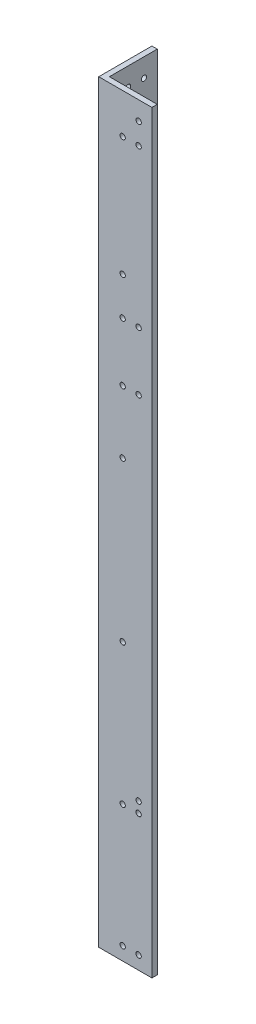
SolidWorks part; units mm, degrees
ref_plane "Front Plane" through (0, 0, 0) normal (0, 0, 1) x (1, 0, 0)
ref_plane "Top Plane" through (0, 0, 0) normal (0, 1, 0) x (1, 0, 0)
ref_plane "Right Plane" through (0, 0, 0) normal (1, 0, 0) x (0, 0, -1)
sketch "Sketch2" plane through (0, 0, 0) normal (0, 1, 0) x (1, 0, 0)
  line L0 (0, 31.75) -> (3.175, 31.75)
  line L1 (3.175, 31.75) -> (3.175, 3.175)
  line L2 (3.175, 3.175) -> (31.75, 3.175)
  line L3 (31.75, 3.175) -> (31.75, 0)
  line L4 (31.75, 0) -> (0, 0)
  line L5 (0, 0) -> (0, 31.75)
  point P9 (1.5875, 31.75)
  point P10 (31.75, 1.5875)
  dimension "D4" = 3.175
  dimension "D1" = 31.75
  dimension "D2" = 31.75
  dimension "D3" = 3.175
extrude "Boss-Extrude1" add sketch "Sketch2" along normal blind 450
sketch "RightSideHoles-Sketch3" plane through (0, 0, 0) normal (0, 0, 1) x (1, 0, 0)
  line L0 (0, 0) -> (31.75, 0) construction
  line L1 (0, 450) -> (31.75, 450) construction
  line L3 (0, 450) -> (0, 0) construction
  circle A0 centre (14.2875, 81.1125) radius 1.5875
  circle A1 centre (23.8125, 81.1125) radius 1.5875
  circle A3 centre (23.8125, 87.4625) radius 1.5875
  circle A5 centre (14.2875, 426.1875) radius 1.5875
  circle A6 centre (23.8125, 438.8875) radius 1.5875
  circle A7 centre (23.8125, 426.1875) radius 1.5875
  circle A8 centre (14.2875, 332.3776) radius 1.5875
  circle A9 centre (23.8125, 332.3776) radius 1.5875
  circle A10 centre (14.2875, 297.4526) radius 1.5875
  circle A11 centre (23.8125, 297.4526) radius 1.5875
  circle A12 centre (14.2875, 7.9375) radius 1.5875
  circle A13 centre (23.8125, 7.9375) radius 1.5875
  circle A14 centre (14.2875, 165) radius 1.5875
  circle A15 centre (14.2875, 260) radius 1.5875
  circle A16 centre (14.2875, 355) radius 1.5875
  dimension "D4" = 3.175
  dimension "D1" = 81.1125
  dimension "D2" = 14.2875
  dimension "D12" = 7.9375
  dimension "D7" = 34.925
  dimension "D3" = 9.525
  dimension "D10" = 332.3776
  dimension "D11" = 165
  dimension "D13" = 95
  dimension "D5" = 6.35
  dimension "D6" = 12.7
  dimension "D8" = 11.1125
  dimension "D9" = 95
sketch "FrontSideHoles-Sketch4" plane through (0, 0, 0) normal (-1, 0, 0) x (0, 0, 1)
  line L0 (-31.75, 450) -> (0, 450) construction
  line L1 (0, 450) -> (0, 0) construction
  line L3 (-31.75, 0) -> (0, 0) construction
  circle A0 centre (-23.8125, 81.1125) radius 1.5875
  circle A2 centre (-23.8125, 87.4625) radius 1.5875
  circle A3 centre (-14.2875, 87.4625) radius 1.5875
  circle A4 centre (-23.8125, 438.8875) radius 1.5875
  circle A5 centre (-14.2875, 438.8875) radius 1.5875
  circle A6 centre (-23.8125, 426.1875) radius 1.5875
  circle A8 centre (-14.2875, 350.0151) radius 2
  circle A9 centre (-14.2875, 309.8151) radius 2
  circle A10 centre (-14.2875, 165) radius 1.5875
  circle A11 centre (-14.2875, 260) radius 1.5875
  circle A13 centre (-23.8125, 7.9375) radius 1.5875
  circle A14 centre (-14.2875, 7.9375) radius 1.5875
  dimension "D4" = 3.175
  dimension "D13" = 95
  dimension "D5" = 6.35
  dimension "D16" = 4
  dimension "D6" = 11.1125
  dimension "D9" = 40.2
  dimension "D10" = 14.2875
  dimension "D7" = 12.7
  dimension "D8" = 309.8151
  dimension "D12" = 165
  dimension "D15" = 7.9375
  dimension "D2" = 14.2875
  dimension "D11" = 9.525
  dimension "D3" = 81.1125
extrude "RightSideHoles-Cut-Extrude1" cut sketch "RightSideHoles-Sketch3" against normal blind 3.175
extrude "FrontSideHoles-Cut-Extrude2" cut sketch "FrontSideHoles-Sketch4" against normal blind 3.175
equation "\"RailThickness\"= .125in'Spec"
equation "\"VSWidth\"= 1.25in'Spec"
equation "\"VSHeight\"= 1.25in'Spec"
equation "\"VSLength\"= 450mm"
equation "\"HoleOffsetFromEdge\"= \"RailThickness\" * 2.5"
equation "\"HoleOffsetFromSide\"= \"RailThickness\" * 3.5"
equation "\"LegHeight\"= 70mm'Space needed for PSU/Stepper/Electronics"
equation "\"VSBottomSideRailHoleY1FromBottomOfLowerRail\"= \"V1 BottomOfLowerRail\" + \"HoleOffsetFromSide\"'Equals 81.1125"
equation "\"VSSideRailHoleX1FromSide\"= \"HoleOffsetFromSide\" + \"RailThickness\""
equation "\"FasteningHoleDiameter\"= .125in"
equation "\"VSBottomSideRailHoleY2FromY1\"= \"LowerRailHeight\" - \"HoleOffsetFromSide\" - \"HoleOffsetFromEdge\"'Equals 6.35"
equation "\"VSTopSideRailHoleY1FromEdge\"= \"HoleOffsetFromEdge\" + \"RailThickness\""
equation "\"D4@RightSideHoles-Sketch3\" = \"FasteningHoleDiameter\""
equation "\"D1@RightSideHoles-Sketch3\" = \"VSBottomSideRailHoleY1FromBottomOfLowerRail\""
equation "\"D2@RightSideHoles-Sketch3\" = \"VSSideRailHoleX1FromSide\""
equation "\"D1@Boss-Extrude1\"=\"VSLength\""
equation "\"D4@FrontSideHoles-Sketch4\" = \"FasteningHoleDiameter\""
equation "\"D6@FrontSideHoles-Sketch4\" = \"VSTopSideRailHoleY1FromEdge\""
equation "\"VSMidSideRailHoleY1FromV8TopOfMidSideRail\"= \"V8 ToTopOfMidSideRail\" - \"HoleOffsetFromEdge\"'Equals 332.37764"
equation "\"LowerRailHeight\"= 1.00in"
equation "\"D2@Sketch2\"=\"VSWidth\""
equation "\"D1@Sketch2\"=\"VSHeight\""
equation "\"TopRailHeight\"= 1.25in"
equation "\"MidLeftOrRightSideRailHeight\"= 2.0in"
equation "\"D12@RightSideHoles-Sketch3\"=\"HoleOffsetFromEdge\""
equation "\"VSMidSideRailHoleY2FromY1\"= \"MidLeftOrRightSideRailHeight\" - \"HoleOffsetFromEdge\" * 2'Equals 34.925"
equation "\"D7@RightSideHoles-Sketch3\"=\"VSMidSideRailHoleY2FromY1\""
equation "\"VSTopSideRailHoleY2FromY1\"= \"TopRailHeight\" - \"VSTopSideRailHoleY1FromEdge\" - \"HoleOffsetFromEdge\"'Equals 12.7"
equation "\"D7@FrontSideHoles-Sketch4\"=\"VSTopSideRailHoleY2FromY1\""
equation "\"VSSideRailHoleX2FromX1\"= \"VSWidth\" - \"VSSideRailHoleX1FromSide\" - \"HoleOffsetFromEdge\""
equation "\"D3@RightSideHoles-Sketch3\"=\"VSSideRailHoleX2FromX1\""
equation "\"1mmSpacer\"= 1mm"
equation "\"20TGT2PulleyWidth\"= 8.7mm'The STL of the Pulley in the diagram is a bit larger"
equation "\"BeltTensionerInnerHeight\"= \"20TGT2PulleyWidth\" * 2 + \"1mmSpacer\" * 3"
equation "\"BeltTensionerHeight\"= 60mm"
equation "\"D9@FrontSideHoles-Sketch4\"=\"VSBeltTensionerHoleY2FromY1\""
equation "\"VSBeltTensionerHoleY1FromBottomAlignedWithYAxisGantryBlockMiddle\"= \"V6 ToMiddleOfYAxisGantryBlock\" - \"MidLeftOrRightSideRailHeight\" / 2 + \"BeltTensionerMountingHoleOffsetFromTopOrBottom\""
equation "\"VSBeltTensionerHoleY2FromY1\"= \"BeltTensionerHeight\" - \"BeltTensionerMountingHoleOffsetFromTopOrBottom\" * 2"
equation "\"V1 BottomOfLowerRail\"= \"LegHeight\""
equation "\"StepperShaftLength\"= 24mm'Pulley will be attached to the end"
equation "\"ZAxisLeadScrewLength\"= 200mm"
equation "\"LM8UUHeight\"= 24mm'Spec"
equation "\"V2 ToBedAtTopOfZAxis\"= \"V1 BottomOfLowerRail\" - \"LowerEnclosureThickness\" + \"StepperShaftLength\" + \"ZAxisLeadScrewLength\" - \"LM8UUHeight\" / 2"
equation "\"HotEndToTopOfXAxisGB\"= 63.315144mm'Measured from the100.Should be 63.315144"
equation "\"TopOfGBToBottomOfLinearRail\"= \"LinearGBWidth\" / 2 + \"LinearRailWidth\" / 2"
equation "\"LinearGBWidth\"= 27mm'Spec"
equation "\"V5 ToBottomOfXAxisLinearRail\"= \"V4 ToTopOfBuildPlate/HotEndTip\" + \"HotEndToTopOfXAxisGB\" - \"TopOfGBToBottomOfLinearRail\""
equation "\"LinearRailWidth\"= 12mm'Spec"
equation "\"V6 ToMiddleOfYAxisGantryBlock\"= \"V5 ToBottomOfXAxisLinearRail\" - \"GABHeight\" / 2'Equals 325.31514"
equation "\"GABUpperHeight\"= 6mm"
equation "\"GABMidWallHeight\"= 28mm'Must equal 28 or changes alignment"
equation "\"D10@RightSideHoles-Sketch3\"=\"VSMidSideRailHoleY1FromV8TopOfMidSideRail\""
equation "\"BedToBuildPlateStandoffLength\"= 15mm"
equation "\"BuildPlateHeight\"= 8mm'Spec"
equation "\"V4 ToTopOfBuildPlate/HotEndTip\"= \"V2 ToBedAtTopOfZAxis\" + \"BedToBuildPlateStandoffLength\" + \"BuildPlateHeight\""
equation "\"D8@FrontSideHoles-Sketch4\"=\"VSBeltTensionerHoleY1FromBottomAlignedWithYAxisGantryBlockMiddle\""
equation "\"V8 ToTopOfMidSideRail\"= \"V6 ToMiddleOfYAxisGantryBlock\" + \"MidSideRailVerticalOffset\""
equation "\"BeltTensionerMountingHoleOffsetFromEdge\"= \"HoleOffsetFromEdge\""
equation "\"VSBeltTensionerXMountingHoleOffsetFromSide\"= \"BeltTensionerMountingHoleOffsetFromEdge\" + \"RailThickness\" * 2"
equation "\"D10@FrontSideHoles-Sketch4\"=\"VSBeltTensionerXMountingHoleOffsetFromSide\""
equation "\"VSEnclosureOffsets\"= ( \"VSLength\" - \"LegHeight\" ) / 4"
equation "\"D11@RightSideHoles-Sketch3\"=\"LegHeight\" + \"VSEnclosureOffsets\""
equation "\"D13@RightSideHoles-Sketch3\"=\"VSEnclosureOffsets\""
equation "\"D12@FrontSideHoles-Sketch4\"= \"LegHeight\" + \"VSEnclosureOffsets\""
equation "\"D13@FrontSideHoles-Sketch4\"=\"VSEnclosureOffsets\""
equation "\"D15@FrontSideHoles-Sketch4\"=\"HoleOffsetFromEdge\""
equation "\"D2@FrontSideHoles-Sketch4\"=\"VSSideRailHoleX1FromSide\""
equation "\"D5@FrontSideHoles-Sketch4\"=\"VSBottomSideRailHoleY2FromY1\""
equation "\"D3@FrontSideHoles-Sketch4\"=\"VSBottomSideRailHoleY1FromBottomOfLowerRail\""
equation "\"D5@RightSideHoles-Sketch3\"=\"VSBottomSideRailHoleY2FromY1\""
equation "\"D6@RightSideHoles-Sketch3\"=\"VSTopSideRailHoleY2FromY1\""
equation "\"D8@RightSideHoles-Sketch3\"=\"VSTopSideRailHoleY1FromEdge\""
equation "\"BeltTensionerMountingHoleDiameter\"= 4.0mm"
equation "\"D16@FrontSideHoles-Sketch4\"=\"BeltTensionerMountingHoleDiameter\""
equation "\"LowerEnclosureThickness\"= 5mm"
equation "\"GABLowerHeight\"= 3mm"
equation "\"GABHeight\"= \"GABLowerHeight\" + \"GABMidWallHeight\" + \"GABUpperHeight\""
equation "\"D9@RightSideHoles-Sketch3\"=\"VSEnclosureOffsets\""
equation "\"BeltTensionerMountingHoleOffsetFromTopOrBottom\"= ( \"BeltTensionerHeight\" - \"BeltTensionerInnerHeight\" ) / 4"
equation "\"MidSideRailVerticalOffset\"= \"LinearRailWidth\" + 3mm'Allows space for RodStabilizer to attach to bottom of MidSideRail"
